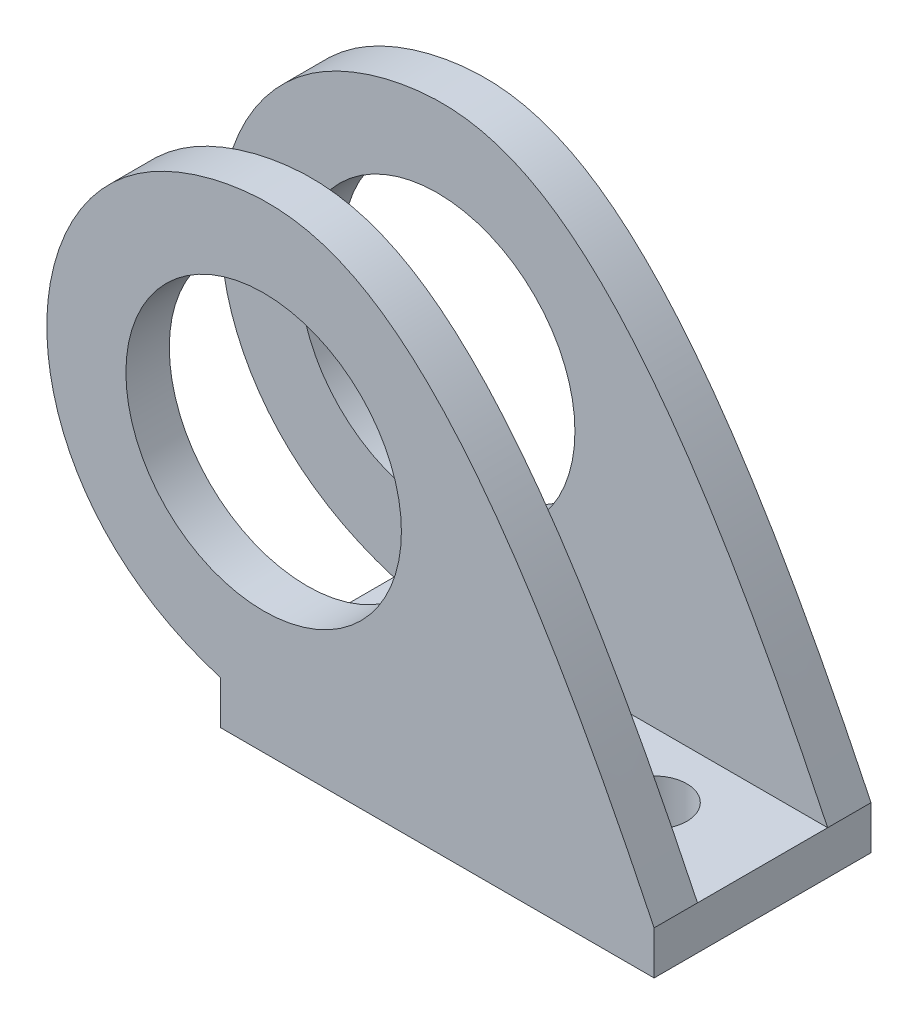
SolidWorks part; units mm, degrees
ref_plane "Front Plane" through (0, 0, 0) normal (0, 0, 1) x (1, 0, 0)
ref_plane "Top Plane" through (0, 0, 0) normal (0, 1, 0) x (1, 0, 0)
ref_plane "Right Plane" through (0, 0, 0) normal (1, 0, 0) x (0, 0, -1)
sketch "Sketch1" plane through (0, 0, 0) normal (0, 1, 0) x (1, 0, 0)
  line L0 (0, 0) -> (0, 0.01) construction
  line L1 (-10, -5) -> (10, -5)
  line L2 (-10, -5) -> (-10, 5)
  line L3 (-10, 5) -> (10, 5)
  line L4 (10, -5) -> (10, 5)
  line L5 (-10, -5) -> (10, 5) construction
  line L6 (-10, 5) -> (10, -5) construction
  line L7 (0, 0.01) -> (5, 0.01) construction
  line L8 (0, 0.01) -> (-5, 0.01) construction
  circle A0 centre (-5, 0.01) radius 1.5
  circle A1 centre (5, 0.01) radius 1.5
  point P0 (0, 0)
  dimension "D1" = 3
  dimension "D2" = 5
  dimension "D3" = 20
  dimension "D4" = 10
extrude "Boss-Extrude1" add sketch "Sketch1" along normal blind 2
sketch "Sketch2" plane through (0, 0, 5) normal (0, 0, 1) x (1, 0, 0)
  line L0 (-8, 12) -> (-8, 0) construction
  line L2 (-10, 2) -> (-10, 0)
  line L3 (-10, 0) -> (10, 0)
  line L4 (10, 0) -> (10, 2)
  circle A0 centre (-8, 12) radius 10 construction
  circle A1 centre (-8, 12) radius 6.35
  spline S0 degree 3 poles (-10, 2) (-19.9343, 5.0089) (-20.0011, 18.402) (-5.4969, 23.5991) (1.4705, 19.8138) (10, 2) knots 0 0 0 0 0.526797 0.626797 1 1 1 1
  point P7 (0, 0)
  dimension "D2" = 12
  dimension "D3" = 12.7
  dimension "D4" = 20
  dimension "D1" = 2
  dimension "D5" = 2
extrude "Boss-Extrude2" add sketch "Sketch2" against normal blind 2
extrude "Boss-Extrude3" add sketch "Sketch2<3>" along normal blind 2 from offset 10 offset against normal yes
sketch "Sketch2<3>" plane through (0, 0, 5) normal (0, 0, 1) x (1, 0, 0) same geometry as "Sketch2"
